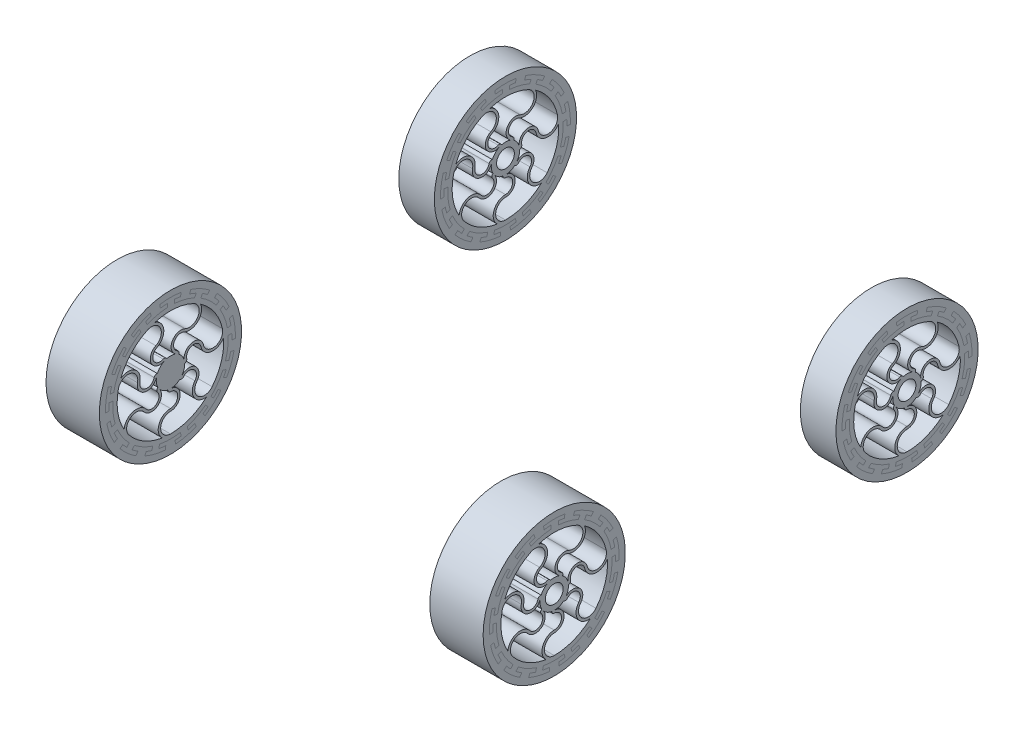
SolidWorks part; units mm, degrees
material "TPU"
ref_plane "Front Plane" through (0, 0, 0) normal (0, 0, 1) x (1, 0, 0)
ref_plane "Top Plane" through (0, 0, 0) normal (0, 1, 0) x (1, 0, 0)
ref_plane "Right Plane" through (0, 0, 0) normal (1, 0, 0) x (0, 0, -1)
ref_plane "Plane1" through (65.3625, 0, 0) normal (1, 0, 0) x (0, 0, -1)
sketch "Sketch1" plane through (65.3625, 0, 0) normal (1, 0, 0) x (0, 0, -1)
  circle A0 centre (0, 0) radius 25.4 construction
  circle A1 centre (0, 0) radius 3.175
  circle A2 centre (0, 0) radius 5.08
  circle A3 centre (0, 0) radius 20.6375
  circle A4 centre (0, 0) radius 19.05
  dimension "D1" = 50.8
  dimension "D2" = 1.5875
  dimension "D3" = 4.7625
  dimension "D4" = 6.35
  dimension "D5" = 10.16
extrude "Boss-Extrude1" add sketch "Sketch1" along normal blind 12.7 contours A3 A4 | A2 A1 region at (65.3625, 0, 4.9363) region at (65.3625, 0, 20.0538)
sketch "Sketch2" plane through (65.3625, 0, 0) normal (1, 0, 0) x (0, 0, -1)
  circle A0 centre (0, 0) radius 5.08
  circle A1 centre (0, 0) radius 19.05
  arc A2 (0, -12.065) -> (0, -5.08) centre (0, -8.5725) ccw
  arc A3 (0, -12.065) -> (0, -19.05) centre (0, -15.5575) ccw
  arc A6 (0, -11.176) -> (-2.919, -18.825) centre (0, -15.5575) ccw
  arc A7 (0, -11.176) -> (0, -5.969) centre (0, -8.5725) ccw
  arc A8 (0, -5.969) -> (-0.8856, -5.0022) centre (0, -5.08) cw
  circle A9 centre (0, 0) radius 19.05 construction
  dimension "D1" = 10.16
  dimension "D3" = 0.889
  dimension "D4" = 0
extrude "Boss-Extrude2" add sketch "Sketch2" along normal up to surface (12.7 mm away) contours A8 A7 A6 A1 A3 A2 A0 region at (65.3625, -11.5929, 0.5056) up to face at (78.0625, 0, -3.175)
pattern_circular "CirPattern1" count 7 over 360 about axis through (78.0625, 0, 0) along (1, 0, 0) of "Boss-Extrude2"
sketch "Sketch3" plane through (65.3625, 0, 0) normal (1, 0, 0) x (0, 0, -1)
  line L2 (-3.81, 22.873) -> (-3.6013, 21.6202)
  line L4 (-1.0968, 21.8907) -> (-1.0968, 20.6083)
  line L6 (3.81, 22.873) -> (3.6013, 21.6202)
  line L7 (1.4432, 21.8706) -> (1.4432, 20.587)
  circle A0 centre (0, 0) radius 20.6375 construction
  circle A1 centre (0, 0) radius 20.6375
  arc A2 (-3.81, 22.873) -> (3.81, 22.873) centre (0, 0) cw
  arc A3 (-3.6013, 21.6202) -> (-1.0968, 21.8907) centre (0, 0) cw
  arc A4 (1.4432, 21.8706) -> (3.6013, 21.6202) centre (0, 0) cw
  point P16 (0, 0)
  point P17 (-3.5825, 23.762)
  dimension "D5" = 2.5401
  dimension "D1" = 2.54
  dimension "D2" = 1.27
  dimension "D3" = 7.62
  dimension "D4" = 2.286
extrude "Boss-Extrude3" add sketch "Sketch3" along a picked direction on the side of the normal blind 12.7 contours A1 L7 L6 A2 L2 A3 L4 region at (65.3625, 22.1515, -0.0444)
pattern_circular "CirPattern2" count 13 over 360 about axis through (78.0625, 0, 0) along (1, 0, 0) of "Boss-Extrude3"
sketch "Sketch5" plane through (65.3625, 0, 0) normal (1, 0, 0) x (0, 0, -1)
  line L36 (-1.0968, 21.8907) -> (-1.0968, 20.6083)
  line L37 (-1.0968, 21.8907) -> (-1.0968, 20.6083)
  line L38 (-3.81, 22.873) -> (-3.6013, 21.6202)
  line L39 (-3.81, 22.873) -> (-3.6013, 21.6202)
  line L40 (3.6013, 21.6202) -> (3.81, 22.873)
  line L41 (3.6013, 21.6202) -> (3.81, 22.873)
  line L42 (1.4432, 20.587) -> (1.4432, 21.8706)
  line L43 (1.4432, 20.587) -> (1.4432, 21.8706)
  line L44 (15.3372, -15.6581) -> (14.4868, -14.6982)
  line L45 (15.3372, -15.6581) -> (14.4868, -14.6982)
  line L46 (18.0194, -14.5942) -> (17.0325, -13.7949)
  line L47 (18.0194, -14.5942) -> (17.0325, -13.7949)
  line L48 (11.6412, -18.5711) -> (12.3158, -19.6472)
  line L49 (11.6412, -18.5711) -> (12.3158, -19.6472)
  line L50 (12.5714, -16.3666) -> (13.4226, -17.3274)
  line L51 (12.5714, -16.3666) -> (13.4226, -17.3274)
  line L52 (6.3037, -20.9921) -> (5.9968, -19.747)
  line L53 (6.3037, -20.9921) -> (5.9968, -19.747)
  line L54 (9.1731, -21.2965) -> (8.6707, -20.1301)
  line L55 (9.1731, -21.2965) -> (8.6707, -20.1301)
  line L56 (1.6774, -21.8538) -> (1.7746, -23.1201)
  line L57 (1.6774, -21.8538) -> (1.7746, -23.1201)
  line L58 (3.5255, -20.3341) -> (3.8327, -21.5804)
  line L59 (3.5255, -20.3341) -> (3.8327, -21.5804)
  line L60 (-4.1738, -21.517) -> (-3.867, -20.272)
  line L61 (-4.1738, -21.517) -> (-3.867, -20.272)
  line L62 (-1.7746, -23.1201) -> (-1.6774, -21.8538)
  line L63 (-1.7746, -23.1201) -> (-1.6774, -21.8538)
  line L64 (-8.6707, -20.1301) -> (-9.1731, -21.2965)
  line L65 (-8.6707, -20.1301) -> (-9.1731, -21.2965)
  line L66 (-6.328, -19.6434) -> (-6.6352, -20.8897)
  line L67 (-6.328, -19.6434) -> (-6.6352, -20.8897)
  line L68 (-13.6952, -17.1127) -> (-12.8449, -16.1529)
  line L69 (-13.6952, -17.1127) -> (-12.8449, -16.1529)
  line L70 (-12.3158, -19.6472) -> (-11.6412, -18.5711)
  line L71 (-12.3158, -19.6472) -> (-11.6412, -18.5711)
  line L108 (-17.0325, -13.7949) -> (-18.0194, -14.5942)
  line L109 (-17.0325, -13.7949) -> (-18.0194, -14.5942)
  line L110 (-14.7319, -14.4526) -> (-15.5831, -15.4133)
  line L111 (-14.7319, -14.4526) -> (-15.5831, -15.4133)
  line L112 (-20.0792, -8.7881) -> (-18.8802, -8.3333)
  line L113 (-20.0792, -8.7881) -> (-18.8802, -8.3333)
  line L114 (-20.0356, -11.6733) -> (-18.9382, -11.0339)
  line L115 (-20.0356, -11.6733) -> (-18.9382, -11.0339)
  line L116 (-21.4923, -4.2993) -> (-22.7376, -4.5485)
  line L117 (-21.4923, -4.2993) -> (-22.7376, -4.5485)
  line L118 (-19.7609, -5.9508) -> (-20.9611, -6.406)
  line L119 (-19.7609, -5.9508) -> (-20.9611, -6.406)
  line L120 (-21.8633, 1.5498) -> (-20.5903, 1.3953)
  line L121 (-21.8633, 1.5498) -> (-20.5903, 1.3953)
  line L122 (-23.1655, -1.0252) -> (-21.8967, -0.969)
  line L123 (-23.1655, -1.0252) -> (-21.8967, -0.969)
  line L124 (-21.0285, 6.1811) -> (-22.247, 6.5393)
  line L125 (-21.0285, 6.1811) -> (-22.247, 6.5393)
  line L126 (-20.2629, 3.9142) -> (-21.5371, 4.0689)
  line L127 (-20.2629, 3.9142) -> (-21.5371, 4.0689)
  line L128 (-18.6387, 11.5327) -> (-17.5834, 10.8042)
  line L129 (-18.6387, 11.5327) -> (-17.5834, 10.8042)
  line L130 (-20.9884, 9.8578) -> (-19.8389, 9.3179)
  line L131 (-20.9884, 9.8578) -> (-19.8389, 9.3179)
  line L132 (-15.7473, 15.2455) -> (-16.6598, 16.1289)
  line L133 (-15.7473, 15.2455) -> (-16.6598, 16.1289)
  line L134 (-16.1229, 12.8825) -> (-17.1793, 13.6116)
  line L135 (-16.1229, 12.8825) -> (-17.1793, 13.6116)
  line L136 (-11.1443, 18.8735) -> (-10.5483, 17.7381)
  line L137 (-11.1443, 18.8735) -> (-10.5483, 17.7381)
  line L138 (-14.0032, 18.4824) -> (-13.2362, 17.4701)
  line L139 (-14.0032, 18.4824) -> (-13.2362, 17.4701)
  line L140 (-6.8586, 20.8174) -> (-7.256, 22.0236)
  line L141 (-6.8586, 20.8174) -> (-7.256, 22.0236)
  line L142 (-8.2894, 18.8995) -> (-8.8859, 20.0361)
  line L143 (-8.2894, 18.8995) -> (-8.8859, 20.0361)
  line L160 (9.2019, 19.8929) -> (8.606, 18.7575)
  line L161 (9.2019, 19.8929) -> (8.606, 18.7575)
  line L162 (7.256, 22.0236) -> (6.8586, 20.8174)
  line L163 (7.256, 22.0236) -> (6.8586, 20.8174)
  line L164 (13.2362, 17.4701) -> (14.0032, 18.4824)
  line L165 (13.2362, 17.4701) -> (14.0032, 18.4824)
  line L166 (10.8451, 17.5582) -> (11.4416, 18.6947)
  line L167 (10.8451, 17.5582) -> (11.4416, 18.6947)
  line L168 (17.3926, 13.338) -> (16.3373, 12.6095)
  line L169 (17.3926, 13.338) -> (16.3373, 12.6095)
  line L170 (16.6598, 16.1289) -> (15.7473, 15.2455)
  line L171 (16.6598, 16.1289) -> (15.7473, 15.2455)
  line L172 (19.8389, 9.3179) -> (20.9884, 9.8578)
  line L173 (19.8389, 9.3179) -> (20.9884, 9.8578)
  line L174 (17.7626, 10.507) -> (18.8189, 11.2362)
  line L175 (17.7626, 10.507) -> (18.8189, 11.2362)
  line L176 (21.5989, 3.7274) -> (20.3259, 3.5729)
  line L177 (21.5989, 3.7274) -> (20.3259, 3.5729)
  line L178 (22.247, 6.5393) -> (21.0285, 6.1811)
  line L179 (22.247, 6.5393) -> (21.0285, 6.1811)
  line L180 (21.8967, -0.969) -> (23.1655, -1.0252)
  line L181 (21.8967, -0.969) -> (23.1655, -1.0252)
  line L182 (20.6108, 1.0488) -> (21.8851, 1.2035)
  line L183 (20.6108, 1.0488) -> (21.8851, 1.2035)
  line L184 (20.8571, -6.737) -> (19.6581, -6.2823)
  line L185 (20.8571, -6.737) -> (19.6581, -6.2823)
  line L186 (22.7376, -4.5485) -> (21.4923, -4.2993)
  line L187 (22.7376, -4.5485) -> (21.4923, -4.2993)
  line L188 (18.9382, -11.0339) -> (20.0356, -11.6733)
  line L189 (18.9382, -11.0339) -> (20.0356, -11.6733)
  line L190 (18.7374, -8.6497) -> (19.9376, -9.1048)
  line L191 (18.7374, -8.6497) -> (19.9376, -9.1048)
  circle A0 centre (0, 0) radius 25.4
  arc A37 (-1.0968, 20.6083) -> (-8.2894, 18.8995) centre (0, 0) ccw
  arc A38 (-1.0968, 21.8907) -> (-3.6013, 21.6202) centre (0, 0) ccw
  arc A39 (-1.0968, 21.8907) -> (-3.6013, 21.6202) centre (0, 0) ccw
  arc A40 (3.81, 22.873) -> (-3.81, 22.873) centre (0, 0) ccw
  arc A41 (3.81, 22.873) -> (-3.81, 22.873) centre (0, 0) ccw
  arc A42 (3.6013, 21.6202) -> (1.4432, 21.8706) centre (0, 0) ccw
  arc A43 (3.6013, 21.6202) -> (1.4432, 21.8706) centre (0, 0) ccw
  arc A44 (8.606, 18.7575) -> (1.4432, 20.587) centre (0, 0) ccw
  arc A45 (8.606, 18.7575) -> (1.4432, 20.587) centre (0, 0) ccw
  arc A46 (15.3372, -15.6581) -> (17.0325, -13.7949) centre (0, 0) ccw
  arc A47 (15.3372, -15.6581) -> (17.0325, -13.7949) centre (0, 0) ccw
  arc A48 (12.3158, -19.6472) -> (18.0194, -14.5942) centre (0, 0) ccw
  arc A49 (12.3158, -19.6472) -> (18.0194, -14.5942) centre (0, 0) ccw
  arc A50 (11.6412, -18.5711) -> (13.4226, -17.3274) centre (0, 0) ccw
  arc A51 (11.6412, -18.5711) -> (13.4226, -17.3274) centre (0, 0) ccw
  arc A52 (5.9968, -19.747) -> (12.5714, -16.3666) centre (0, 0) ccw
  arc A53 (5.9968, -19.747) -> (12.5714, -16.3666) centre (0, 0) ccw
  arc A54 (6.3037, -20.9921) -> (8.6707, -20.1301) centre (0, 0) ccw
  arc A55 (6.3037, -20.9921) -> (8.6707, -20.1301) centre (0, 0) ccw
  arc A56 (1.7746, -23.1201) -> (9.1731, -21.2965) centre (0, 0) ccw
  arc A57 (1.7746, -23.1201) -> (9.1731, -21.2965) centre (0, 0) ccw
  arc A58 (1.6774, -21.8538) -> (3.8327, -21.5804) centre (0, 0) ccw
  arc A59 (1.6774, -21.8538) -> (3.8327, -21.5804) centre (0, 0) ccw
  arc A60 (-3.867, -20.272) -> (3.5255, -20.3341) centre (0, 0) ccw
  arc A61 (-3.867, -20.272) -> (3.5255, -20.3341) centre (0, 0) ccw
  arc A62 (-4.1738, -21.517) -> (-1.6774, -21.8538) centre (0, 0) ccw
  arc A63 (-4.1738, -21.517) -> (-1.6774, -21.8538) centre (0, 0) ccw
  arc A64 (-9.1731, -21.2965) -> (-1.7746, -23.1201) centre (0, 0) ccw
  arc A65 (-9.1731, -21.2965) -> (-1.7746, -23.1201) centre (0, 0) ccw
  arc A66 (-8.6707, -20.1301) -> (-6.6352, -20.8897) centre (0, 0) ccw
  arc A67 (-8.6707, -20.1301) -> (-6.6352, -20.8897) centre (0, 0) ccw
  arc A68 (-12.8449, -16.1529) -> (-6.328, -19.6434) centre (0, 0) ccw
  arc A69 (-12.8449, -16.1529) -> (-6.328, -19.6434) centre (0, 0) ccw
  arc A70 (-13.6952, -17.1127) -> (-11.6412, -18.5711) centre (0, 0) ccw
  arc A71 (-13.6952, -17.1127) -> (-11.6412, -18.5711) centre (0, 0) ccw
  arc A72 (-18.0194, -14.5942) -> (-12.3158, -19.6472) centre (0, 0) ccw
  arc A73 (-1.0968, 20.6083) -> (-8.2894, 18.8995) centre (0, 0) ccw
  arc A109 (-18.0194, -14.5942) -> (-12.3158, -19.6472) centre (0, 0) ccw
  arc A110 (-17.0325, -13.7949) -> (-15.5831, -15.4133) centre (0, 0) ccw
  arc A111 (-17.0325, -13.7949) -> (-15.5831, -15.4133) centre (0, 0) ccw
  arc A112 (-18.8802, -8.3333) -> (-14.7319, -14.4526) centre (0, 0) ccw
  arc A113 (-18.8802, -8.3333) -> (-14.7319, -14.4526) centre (0, 0) ccw
  arc A114 (-20.0792, -8.7881) -> (-18.9382, -11.0339) centre (0, 0) ccw
  arc A115 (-20.0792, -8.7881) -> (-18.9382, -11.0339) centre (0, 0) ccw
  arc A116 (-22.7376, -4.5485) -> (-20.0356, -11.6733) centre (0, 0) ccw
  arc A117 (-22.7376, -4.5485) -> (-20.0356, -11.6733) centre (0, 0) ccw
  arc A118 (-21.4923, -4.2993) -> (-20.9611, -6.406) centre (0, 0) ccw
  arc A119 (-21.4923, -4.2993) -> (-20.9611, -6.406) centre (0, 0) ccw
  arc A120 (-20.5903, 1.3953) -> (-19.7609, -5.9508) centre (0, 0) ccw
  arc A121 (-20.5903, 1.3953) -> (-19.7609, -5.9508) centre (0, 0) ccw
  arc A122 (-21.8633, 1.5498) -> (-21.8967, -0.969) centre (0, 0) ccw
  arc A123 (-21.8633, 1.5498) -> (-21.8967, -0.969) centre (0, 0) ccw
  arc A124 (-22.247, 6.5393) -> (-23.1655, -1.0252) centre (0, 0) ccw
  arc A125 (-22.247, 6.5393) -> (-23.1655, -1.0252) centre (0, 0) ccw
  arc A126 (-21.0285, 6.1811) -> (-21.5371, 4.0689) centre (0, 0) ccw
  arc A127 (-21.0285, 6.1811) -> (-21.5371, 4.0689) centre (0, 0) ccw
  arc A128 (-17.5834, 10.8042) -> (-20.2629, 3.9142) centre (0, 0) ccw
  arc A129 (-17.5834, 10.8042) -> (-20.2629, 3.9142) centre (0, 0) ccw
  arc A130 (-18.6387, 11.5327) -> (-19.8389, 9.3179) centre (0, 0) ccw
  arc A131 (-18.6387, 11.5327) -> (-19.8389, 9.3179) centre (0, 0) ccw
  arc A132 (-16.6598, 16.1289) -> (-20.9884, 9.8578) centre (0, 0) ccw
  arc A133 (-16.6598, 16.1289) -> (-20.9884, 9.8578) centre (0, 0) ccw
  arc A134 (-15.7473, 15.2455) -> (-17.1793, 13.6116) centre (0, 0) ccw
  arc A135 (-15.7473, 15.2455) -> (-17.1793, 13.6116) centre (0, 0) ccw
  arc A136 (-10.5483, 17.7381) -> (-16.1229, 12.8825) centre (0, 0) ccw
  arc A137 (-10.5483, 17.7381) -> (-16.1229, 12.8825) centre (0, 0) ccw
  arc A138 (-11.1443, 18.8735) -> (-13.2362, 17.4701) centre (0, 0) ccw
  arc A139 (-11.1443, 18.8735) -> (-13.2362, 17.4701) centre (0, 0) ccw
  arc A140 (-7.256, 22.0236) -> (-14.0032, 18.4824) centre (0, 0) ccw
  arc A141 (-7.256, 22.0236) -> (-14.0032, 18.4824) centre (0, 0) ccw
  arc A142 (-6.8586, 20.8174) -> (-8.8859, 20.0361) centre (0, 0) ccw
  arc A143 (-6.8586, 20.8174) -> (-8.8859, 20.0361) centre (0, 0) ccw
  arc A160 (9.2019, 19.8929) -> (6.8586, 20.8174) centre (0, 0) ccw
  arc A161 (9.2019, 19.8929) -> (6.8586, 20.8174) centre (0, 0) ccw
  arc A162 (14.0032, 18.4824) -> (7.256, 22.0236) centre (0, 0) ccw
  arc A163 (14.0032, 18.4824) -> (7.256, 22.0236) centre (0, 0) ccw
  arc A164 (13.2362, 17.4701) -> (11.4416, 18.6947) centre (0, 0) ccw
  arc A165 (13.2362, 17.4701) -> (11.4416, 18.6947) centre (0, 0) ccw
  arc A166 (16.3373, 12.6095) -> (10.8451, 17.5582) centre (0, 0) ccw
  arc A167 (16.3373, 12.6095) -> (10.8451, 17.5582) centre (0, 0) ccw
  arc A168 (17.3926, 13.338) -> (15.7473, 15.2455) centre (0, 0) ccw
  arc A169 (17.3926, 13.338) -> (15.7473, 15.2455) centre (0, 0) ccw
  arc A170 (20.9884, 9.8578) -> (16.6598, 16.1289) centre (0, 0) ccw
  arc A171 (20.9884, 9.8578) -> (16.6598, 16.1289) centre (0, 0) ccw
  arc A172 (19.8389, 9.3179) -> (18.8189, 11.2362) centre (0, 0) ccw
  arc A173 (19.8389, 9.3179) -> (18.8189, 11.2362) centre (0, 0) ccw
  arc A174 (20.3259, 3.5729) -> (17.7626, 10.507) centre (0, 0) ccw
  arc A175 (20.3259, 3.5729) -> (17.7626, 10.507) centre (0, 0) ccw
  arc A176 (21.5989, 3.7274) -> (21.0285, 6.1811) centre (0, 0) ccw
  arc A177 (21.5989, 3.7274) -> (21.0285, 6.1811) centre (0, 0) ccw
  arc A178 (23.1655, -1.0252) -> (22.247, 6.5393) centre (0, 0) ccw
  arc A179 (23.1655, -1.0252) -> (22.247, 6.5393) centre (0, 0) ccw
  arc A180 (21.8967, -0.969) -> (21.8851, 1.2035) centre (0, 0) ccw
  arc A181 (21.8967, -0.969) -> (21.8851, 1.2035) centre (0, 0) ccw
  arc A182 (19.6581, -6.2823) -> (20.6108, 1.0488) centre (0, 0) ccw
  arc A183 (19.6581, -6.2823) -> (20.6108, 1.0488) centre (0, 0) ccw
  arc A184 (20.8571, -6.737) -> (21.4923, -4.2993) centre (0, 0) ccw
  arc A185 (20.8571, -6.737) -> (21.4923, -4.2993) centre (0, 0) ccw
  arc A186 (20.0356, -11.6733) -> (22.7376, -4.5485) centre (0, 0) ccw
  arc A187 (20.0356, -11.6733) -> (22.7376, -4.5485) centre (0, 0) ccw
  arc A188 (18.9382, -11.0339) -> (19.9376, -9.1048) centre (0, 0) ccw
  arc A189 (18.9382, -11.0339) -> (19.9376, -9.1048) centre (0, 0) ccw
  arc A190 (14.4868, -14.6982) -> (18.7374, -8.6497) centre (0, 0) ccw
  arc A191 (14.4868, -14.6982) -> (18.7374, -8.6497) centre (0, 0) ccw
  dimension "D1" = 50.8
  dimension "D2" = 0
extrude "Boss-Extrude4" add sketch "Sketch5" along normal up to surface (12.7 mm away) separate body up to face at (78.0625, -9.1625, 4.7382)
sketch "Sketch4" plane through (0, 0, 0) normal (1, 0, 0) x (0, 0, -1)
  line L0 (0, 0) -> (-126, 0) construction
pattern_linear "LPattern1" count 2 spacing 126 along (0, 0, 1) of bodies 111 107
sketch "Sketch6" plane through (65.3625, 0, 0) normal (-1, 0, 0) x (0, 0, 1)
  line L36 (127.0968, 20.6083) -> (127.0968, 21.8907)
  line L37 (129.6013, 21.6202) -> (129.81, 22.873)
  line L38 (122.19, 22.873) -> (122.3987, 21.6202)
  line L39 (124.5568, 21.8706) -> (124.5568, 20.587)
  line L40 (111.5132, -14.6982) -> (110.6628, -15.6581)
  line L41 (108.9675, -13.7949) -> (107.9806, -14.5942)
  line L42 (113.6842, -19.6472) -> (114.3588, -18.5711)
  line L43 (112.5774, -17.3274) -> (113.4286, -16.3666)
  line L44 (120.0032, -19.747) -> (119.6963, -20.9921)
  line L45 (117.3293, -20.1301) -> (116.8268, -21.2965)
  line L46 (124.2254, -23.1201) -> (124.3226, -21.8538)
  line L47 (122.1673, -21.5804) -> (122.4745, -20.3341)
  line L48 (129.867, -20.272) -> (130.1738, -21.517)
  line L49 (127.6774, -21.8538) -> (127.7746, -23.1201)
  line L50 (135.1731, -21.2965) -> (134.6707, -20.1301)
  line L51 (132.6352, -20.8897) -> (132.328, -19.6434)
  line L52 (138.8449, -16.1529) -> (139.6952, -17.1127)
  line L53 (137.6412, -18.5711) -> (138.3158, -19.6472)
  line L54 (144.0194, -14.5942) -> (143.0325, -13.7949)
  line L55 (141.5831, -15.4133) -> (140.7319, -14.4526)
  line L56 (144.8802, -8.3333) -> (146.0792, -8.7881)
  line L57 (144.9382, -11.0339) -> (146.0356, -11.6733)
  line L58 (148.7376, -4.5485) -> (147.4923, -4.2993)
  line L59 (146.9611, -6.406) -> (145.7609, -5.9508)
  line L60 (146.5903, 1.3953) -> (147.8633, 1.5498)
  line L61 (147.8967, -0.969) -> (149.1654, -1.0252)
  line L62 (148.247, 6.5393) -> (147.0285, 6.1811)
  line L63 (147.5371, 4.0689) -> (146.2629, 3.9142)
  line L64 (143.5834, 10.8042) -> (144.6387, 11.5327)
  line L65 (145.8389, 9.3179) -> (146.9884, 9.8578)
  line L66 (142.6598, 16.1289) -> (141.7473, 15.2455)
  line L67 (143.1793, 13.6116) -> (142.1229, 12.8825)
  line L68 (136.5483, 17.7381) -> (137.1443, 18.8735)
  line L69 (139.2362, 17.4701) -> (140.0032, 18.4824)
  line L70 (133.256, 22.0236) -> (132.8586, 20.8174)
  line L71 (134.8859, 20.0361) -> (134.2894, 18.8995)
  line L72 (127.0968, 20.6083) -> (127.0968, 21.8907)
  line L73 (129.6013, 21.6202) -> (129.81, 22.873)
  line L74 (122.19, 22.873) -> (122.3987, 21.6202)
  line L75 (124.5568, 21.8706) -> (124.5568, 20.587)
  line L76 (111.5132, -14.6982) -> (110.6628, -15.6581)
  line L77 (108.9675, -13.7949) -> (107.9806, -14.5942)
  line L78 (113.6842, -19.6472) -> (114.3588, -18.5711)
  line L79 (112.5774, -17.3274) -> (113.4286, -16.3666)
  line L80 (120.0032, -19.747) -> (119.6963, -20.9921)
  line L81 (117.3293, -20.1301) -> (116.8268, -21.2965)
  line L82 (124.2254, -23.1201) -> (124.3226, -21.8538)
  line L83 (122.1673, -21.5804) -> (122.4745, -20.3341)
  line L84 (129.867, -20.272) -> (130.1738, -21.517)
  line L85 (127.6774, -21.8538) -> (127.7746, -23.1201)
  line L86 (135.1731, -21.2965) -> (134.6707, -20.1301)
  line L87 (132.6352, -20.8897) -> (132.328, -19.6434)
  line L88 (138.8449, -16.1529) -> (139.6952, -17.1127)
  line L89 (137.6412, -18.5711) -> (138.3158, -19.6472)
  line L90 (144.0194, -14.5942) -> (143.0325, -13.7949)
  line L91 (141.5831, -15.4133) -> (140.7319, -14.4526)
  line L92 (144.8802, -8.3333) -> (146.0792, -8.7881)
  line L93 (144.9382, -11.0339) -> (146.0356, -11.6733)
  line L94 (148.7376, -4.5485) -> (147.4923, -4.2993)
  line L95 (146.9611, -6.406) -> (145.7609, -5.9508)
  line L96 (146.5903, 1.3953) -> (147.8633, 1.5498)
  line L97 (147.8967, -0.969) -> (149.1654, -1.0252)
  line L98 (148.247, 6.5393) -> (147.0285, 6.1811)
  line L99 (147.5371, 4.0689) -> (146.2629, 3.9142)
  line L100 (143.5834, 10.8042) -> (144.6387, 11.5327)
  line L101 (145.8389, 9.3179) -> (146.9884, 9.8578)
  line L102 (142.6598, 16.1289) -> (141.7473, 15.2455)
  line L103 (143.1793, 13.6116) -> (142.1229, 12.8825)
  line L104 (136.5483, 17.7381) -> (137.1443, 18.8735)
  line L105 (139.2362, 17.4701) -> (140.0032, 18.4824)
  line L106 (133.256, 22.0236) -> (132.8586, 20.8174)
  line L107 (134.8859, 20.0361) -> (134.2894, 18.8995)
  line L124 (117.394, 18.7575) -> (116.7981, 19.8929)
  line L125 (117.394, 18.7575) -> (116.7981, 19.8929)
  line L126 (119.1414, 20.8174) -> (118.744, 22.0236)
  line L127 (119.1414, 20.8174) -> (118.744, 22.0236)
  line L128 (111.9968, 18.4824) -> (112.7638, 17.4701)
  line L129 (111.9968, 18.4824) -> (112.7638, 17.4701)
  line L130 (114.5584, 18.6947) -> (115.1549, 17.5582)
  line L131 (114.5584, 18.6947) -> (115.1549, 17.5582)
  line L132 (109.6627, 12.6095) -> (108.6074, 13.338)
  line L133 (109.6627, 12.6095) -> (108.6074, 13.338)
  line L134 (110.2527, 15.2455) -> (109.3402, 16.1289)
  line L135 (110.2527, 15.2455) -> (109.3402, 16.1289)
  line L136 (105.0116, 9.8578) -> (106.1611, 9.3179)
  line L137 (105.0116, 9.8578) -> (106.1611, 9.3179)
  line L138 (107.1811, 11.2362) -> (108.2374, 10.507)
  line L139 (107.1811, 11.2362) -> (108.2374, 10.507)
  line L140 (105.6741, 3.5729) -> (104.4011, 3.7274)
  line L141 (105.6741, 3.5729) -> (104.4011, 3.7274)
  line L142 (104.9715, 6.1811) -> (103.753, 6.5393)
  line L143 (104.9715, 6.1811) -> (103.753, 6.5393)
  line L144 (102.8345, -1.0252) -> (104.1033, -0.969)
  line L145 (102.8345, -1.0252) -> (104.1033, -0.969)
  line L146 (104.1149, 1.2035) -> (105.3892, 1.0488)
  line L147 (104.1149, 1.2035) -> (105.3892, 1.0488)
  line L148 (106.3419, -6.2823) -> (105.1429, -6.737)
  line L149 (106.3419, -6.2823) -> (105.1429, -6.737)
  line L150 (104.5077, -4.2993) -> (103.2623, -4.5485)
  line L151 (104.5077, -4.2993) -> (103.2623, -4.5485)
  line L152 (105.9644, -11.6733) -> (107.0618, -11.0339)
  line L153 (105.9644, -11.6733) -> (107.0618, -11.0339)
  line L154 (106.0624, -9.1048) -> (107.2626, -8.6497)
  line L155 (106.0624, -9.1048) -> (107.2626, -8.6497)
  arc A36 (134.2894, 18.8995) -> (127.0968, 20.6083) centre (126, 0) ccw
  arc A37 (129.6013, 21.6202) -> (127.0968, 21.8907) centre (126, 0) ccw
  arc A38 (129.81, 22.873) -> (122.19, 22.873) centre (126, 0) ccw
  arc A39 (124.5568, 21.8706) -> (122.3987, 21.6202) centre (126, 0) ccw
  arc A40 (124.5568, 20.587) -> (117.394, 18.7575) centre (126, 0) ccw
  arc A41 (108.9675, -13.7949) -> (110.6628, -15.6581) centre (126, 0) ccw
  arc A42 (107.9806, -14.5942) -> (113.6842, -19.6472) centre (126, 0) ccw
  arc A43 (112.5774, -17.3274) -> (114.3588, -18.5711) centre (126, 0) ccw
  arc A44 (113.4286, -16.3666) -> (120.0032, -19.747) centre (126, 0) ccw
  arc A45 (117.3293, -20.1301) -> (119.6963, -20.9921) centre (126, 0) ccw
  arc A46 (116.8268, -21.2965) -> (124.2254, -23.1201) centre (126, 0) ccw
  arc A47 (122.1673, -21.5804) -> (124.3226, -21.8538) centre (126, 0) ccw
  arc A48 (122.4745, -20.3341) -> (129.867, -20.272) centre (126, 0) ccw
  arc A49 (127.6774, -21.8538) -> (130.1738, -21.517) centre (126, 0) ccw
  arc A50 (127.7746, -23.1201) -> (135.1731, -21.2965) centre (126, 0) ccw
  arc A51 (132.6352, -20.8897) -> (134.6707, -20.1301) centre (126, 0) ccw
  arc A52 (132.328, -19.6434) -> (138.8449, -16.1529) centre (126, 0) ccw
  arc A53 (137.6412, -18.5711) -> (139.6952, -17.1127) centre (126, 0) ccw
  arc A54 (138.3158, -19.6472) -> (144.0194, -14.5942) centre (126, 0) ccw
  arc A55 (141.5831, -15.4133) -> (143.0325, -13.7949) centre (126, 0) ccw
  arc A56 (140.7319, -14.4526) -> (144.8802, -8.3333) centre (126, 0) ccw
  arc A57 (144.9382, -11.0339) -> (146.0792, -8.7881) centre (126, 0) ccw
  arc A58 (146.0356, -11.6733) -> (148.7376, -4.5485) centre (126, 0) ccw
  arc A59 (146.9611, -6.406) -> (147.4923, -4.2993) centre (126, 0) ccw
  arc A60 (145.7609, -5.9508) -> (146.5903, 1.3953) centre (126, 0) ccw
  arc A61 (147.8967, -0.969) -> (147.8633, 1.5498) centre (126, 0) ccw
  arc A62 (149.1654, -1.0252) -> (148.247, 6.5393) centre (126, 0) ccw
  arc A63 (147.5371, 4.0689) -> (147.0285, 6.1811) centre (126, 0) ccw
  arc A64 (146.2629, 3.9142) -> (143.5834, 10.8042) centre (126, 0) ccw
  arc A65 (145.8389, 9.3179) -> (144.6387, 11.5327) centre (126, 0) ccw
  arc A66 (146.9884, 9.8578) -> (142.6598, 16.1289) centre (126, 0) ccw
  arc A67 (143.1793, 13.6116) -> (141.7473, 15.2455) centre (126, 0) ccw
  arc A68 (142.1229, 12.8825) -> (136.5483, 17.7381) centre (126, 0) ccw
  arc A69 (139.2362, 17.4701) -> (137.1443, 18.8735) centre (126, 0) ccw
  arc A70 (140.0032, 18.4824) -> (133.256, 22.0236) centre (126, 0) ccw
  arc A71 (134.8859, 20.0361) -> (132.8586, 20.8174) centre (126, 0) ccw
  arc A72 (134.2894, 18.8995) -> (127.0968, 20.6083) centre (126, 0) ccw
  arc A73 (129.6013, 21.6202) -> (127.0968, 21.8907) centre (126, 0) ccw
  arc A74 (129.81, 22.873) -> (122.19, 22.873) centre (126, 0) ccw
  arc A75 (124.5568, 21.8706) -> (122.3987, 21.6202) centre (126, 0) ccw
  arc A76 (124.5568, 20.587) -> (117.394, 18.7575) centre (126, 0) ccw
  arc A77 (108.9675, -13.7949) -> (110.6628, -15.6581) centre (126, 0) ccw
  arc A78 (107.9806, -14.5942) -> (113.6842, -19.6472) centre (126, 0) ccw
  arc A79 (112.5774, -17.3274) -> (114.3588, -18.5711) centre (126, 0) ccw
  arc A80 (113.4286, -16.3666) -> (120.0032, -19.747) centre (126, 0) ccw
  arc A81 (117.3293, -20.1301) -> (119.6963, -20.9921) centre (126, 0) ccw
  arc A82 (116.8268, -21.2965) -> (124.2254, -23.1201) centre (126, 0) ccw
  arc A83 (122.1673, -21.5804) -> (124.3226, -21.8538) centre (126, 0) ccw
  arc A84 (122.4745, -20.3341) -> (129.867, -20.272) centre (126, 0) ccw
  arc A85 (127.6774, -21.8538) -> (130.1738, -21.517) centre (126, 0) ccw
  arc A86 (127.7746, -23.1201) -> (135.1731, -21.2965) centre (126, 0) ccw
  arc A87 (132.6352, -20.8897) -> (134.6707, -20.1301) centre (126, 0) ccw
  arc A88 (132.328, -19.6434) -> (138.8449, -16.1529) centre (126, 0) ccw
  arc A89 (137.6412, -18.5711) -> (139.6952, -17.1127) centre (126, 0) ccw
  arc A90 (138.3158, -19.6472) -> (144.0194, -14.5942) centre (126, 0) ccw
  arc A91 (141.5831, -15.4133) -> (143.0325, -13.7949) centre (126, 0) ccw
  arc A92 (140.7319, -14.4526) -> (144.8802, -8.3333) centre (126, 0) ccw
  arc A93 (144.9382, -11.0339) -> (146.0792, -8.7881) centre (126, 0) ccw
  arc A94 (146.0356, -11.6733) -> (148.7376, -4.5485) centre (126, 0) ccw
  arc A95 (146.9611, -6.406) -> (147.4923, -4.2993) centre (126, 0) ccw
  arc A96 (145.7609, -5.9508) -> (146.5903, 1.3953) centre (126, 0) ccw
  arc A97 (147.8967, -0.969) -> (147.8633, 1.5498) centre (126, 0) ccw
  arc A98 (149.1654, -1.0252) -> (148.247, 6.5393) centre (126, 0) ccw
  arc A99 (147.5371, 4.0689) -> (147.0285, 6.1811) centre (126, 0) ccw
  arc A100 (146.2629, 3.9142) -> (143.5834, 10.8042) centre (126, 0) ccw
  arc A101 (145.8389, 9.3179) -> (144.6387, 11.5327) centre (126, 0) ccw
  arc A102 (146.9884, 9.8578) -> (142.6598, 16.1289) centre (126, 0) ccw
  arc A103 (143.1793, 13.6116) -> (141.7473, 15.2455) centre (126, 0) ccw
  arc A104 (142.1229, 12.8825) -> (136.5483, 17.7381) centre (126, 0) ccw
  arc A105 (139.2362, 17.4701) -> (137.1443, 18.8735) centre (126, 0) ccw
  arc A106 (140.0032, 18.4824) -> (133.256, 22.0236) centre (126, 0) ccw
  arc A107 (134.8859, 20.0361) -> (132.8586, 20.8174) centre (126, 0) ccw
  arc A124 (119.1414, 20.8174) -> (116.7981, 19.8929) centre (126, 0) ccw
  arc A125 (119.1414, 20.8174) -> (116.7981, 19.8929) centre (126, 0) ccw
  arc A126 (118.744, 22.0236) -> (111.9968, 18.4824) centre (126, 0) ccw
  arc A127 (118.744, 22.0236) -> (111.9968, 18.4824) centre (126, 0) ccw
  arc A128 (114.5584, 18.6947) -> (112.7638, 17.4701) centre (126, 0) ccw
  arc A129 (114.5584, 18.6947) -> (112.7638, 17.4701) centre (126, 0) ccw
  arc A130 (115.1549, 17.5582) -> (109.6627, 12.6095) centre (126, 0) ccw
  arc A131 (115.1549, 17.5582) -> (109.6627, 12.6095) centre (126, 0) ccw
  arc A132 (110.2527, 15.2455) -> (108.6074, 13.338) centre (126, 0) ccw
  arc A133 (110.2527, 15.2455) -> (108.6074, 13.338) centre (126, 0) ccw
  arc A134 (109.3402, 16.1289) -> (105.0116, 9.8578) centre (126, 0) ccw
  arc A135 (109.3402, 16.1289) -> (105.0116, 9.8578) centre (126, 0) ccw
  arc A136 (107.1811, 11.2362) -> (106.1611, 9.3179) centre (126, 0) ccw
  arc A137 (107.1811, 11.2362) -> (106.1611, 9.3179) centre (126, 0) ccw
  arc A138 (108.2374, 10.507) -> (105.6741, 3.5729) centre (126, 0) ccw
  arc A139 (108.2374, 10.507) -> (105.6741, 3.5729) centre (126, 0) ccw
  arc A140 (104.9715, 6.1811) -> (104.4011, 3.7274) centre (126, 0) ccw
  arc A141 (104.9715, 6.1811) -> (104.4011, 3.7274) centre (126, 0) ccw
  arc A142 (103.753, 6.5393) -> (102.8345, -1.0252) centre (126, 0) ccw
  arc A143 (103.753, 6.5393) -> (102.8345, -1.0252) centre (126, 0) ccw
  arc A144 (104.1149, 1.2035) -> (104.1033, -0.969) centre (126, 0) ccw
  arc A145 (104.1149, 1.2035) -> (104.1033, -0.969) centre (126, 0) ccw
  arc A146 (105.3892, 1.0488) -> (106.3419, -6.2823) centre (126, 0) ccw
  arc A147 (105.3892, 1.0488) -> (106.3419, -6.2823) centre (126, 0) ccw
  arc A148 (104.5077, -4.2993) -> (105.1429, -6.737) centre (126, 0) ccw
  arc A149 (104.5077, -4.2993) -> (105.1429, -6.737) centre (126, 0) ccw
  arc A150 (103.2623, -4.5485) -> (105.9644, -11.6733) centre (126, 0) ccw
  arc A151 (103.2623, -4.5485) -> (105.9644, -11.6733) centre (126, 0) ccw
  arc A152 (106.0624, -9.1048) -> (107.0618, -11.0339) centre (126, 0) ccw
  arc A153 (106.0624, -9.1048) -> (107.0618, -11.0339) centre (126, 0) ccw
  arc A154 (107.2626, -8.6497) -> (111.5132, -14.6982) centre (126, 0) ccw
  arc A155 (107.2626, -8.6497) -> (111.5132, -14.6982) centre (126, 0) ccw
  dimension "D1" = 0
extrude "Boss-Extrude6" add sketch "Sketch6" along normal up to surface (6.35 mm away)
sketch "Sketch9" plane through (65.3625, 0, 0) normal (1, 0, 0) x (0, 0, -1)
  arc A0 (-128.2041, 4.5769) -> (-130.6797, 1.9765) centre (-126, 0) ccw construction
  arc A1 (-131.2348, 10.8702) -> (-128.2041, 4.5769) centre (-129.7195, 7.7236) ccw construction
  arc A2 (-131.2348, 10.8702) -> (-134.2655, 17.1635) centre (-132.7501, 14.0168) ccw construction
  arc A3 (-134.2655, 17.1635) -> (-143.7035, 7.0348) centre (-126, 0) ccw construction
  arc A4 (-136.8958, 2.4869) -> (-143.7035, 7.0348) centre (-141.1674, 3.4619) ccw construction
  arc A5 (-136.8958, 2.4869) -> (-131.8193, 1.3282) centre (-134.3576, 1.9076) ccw construction
  arc A6 (-130.6797, 1.9765) -> (-131.8193, 1.3282) centre (-130.9526, 1.1304) ccw construction
  arc A7 (-130.9526, 1.1304) -> (-130.463, -2.4264) centre (-126, 0) ccw construction
  arc A8 (-137.7625, 2.6847) -> (-130.9526, 1.1304) centre (-134.3576, 1.9076) ccw construction
  arc A9 (-137.7625, 2.6847) -> (-144.5724, 4.239) centre (-141.1674, 3.4619) ccw construction
  arc A10 (-144.5724, 4.239) -> (-142.538, -9.455) centre (-126, 0) ccw construction
  arc A11 (-134.7377, -6.9681) -> (-142.538, -9.455) centre (-138.1633, -9.6999) ccw construction
  arc A12 (-134.7377, -6.9681) -> (-130.6668, -3.7216) centre (-132.7022, -5.3449) ccw construction
  arc A13 (-130.463, -2.4264) -> (-130.6668, -3.7216) centre (-129.9717, -3.1673) ccw construction
  arc A14 (-140.8939, -11.8775) -> (-128.919, -18.825) centre (-126, 0) ccw construction
  arc A15 (-126, -11.176) -> (-128.919, -18.825) centre (-126, -15.5575) ccw construction
  arc A16 (-126, -11.176) -> (-126, -5.969) centre (-126, -8.5725) ccw construction
  arc A17 (-126.8856, -5.0022) -> (-126, -5.969) centre (-126, -5.08) ccw construction
  arc A18 (-129.9717, -3.1673) -> (-126.8856, -5.0022) centre (-126, 0) ccw construction
  arc A19 (-135.4328, -7.5224) -> (-129.9717, -3.1673) centre (-132.7022, -5.3449) ccw construction
  arc A20 (-135.4328, -7.5224) -> (-140.8939, -11.8775) centre (-138.1633, -9.6999) ccw construction
  arc A21 (-126, -12.065) -> (-126, -19.05) centre (-126, -15.5575) ccw construction
  arc A22 (-126, -19.05) -> (-113.102, -14.0194) centre (-126, 0) ccw construction
  arc A23 (-117.2623, -6.9681) -> (-113.102, -14.0194) centre (-113.8367, -9.6999) ccw construction
  arc A24 (-117.2623, -6.9681) -> (-121.3332, -3.7216) centre (-119.2977, -5.3449) ccw construction
  arc A25 (-122.6413, -3.8112) -> (-121.3332, -3.7216) centre (-122.0283, -3.1673) ccw construction
  arc A26 (-126, -5.08) -> (-122.6413, -3.8112) centre (-126, 0) ccw construction
  arc A27 (-126, -12.065) -> (-126, -5.08) centre (-126, -8.5725) ccw construction
  arc A28 (-122.0283, -3.1673) -> (-120.9261, 0.2497) centre (-126, 0) ccw construction
  arc A29 (-116.5672, -7.5224) -> (-122.0283, -3.1673) centre (-119.2977, -5.3449) ccw construction
  arc A30 (-116.5672, -7.5224) -> (-111.1061, -11.8775) centre (-113.8367, -9.6999) ccw construction
  arc A31 (-111.1061, -11.8775) -> (-106.9974, 1.3431) centre (-126, 0) ccw construction
  arc A32 (-115.1042, 2.4869) -> (-106.9974, 1.3431) centre (-110.8326, 3.4619) ccw construction
  arc A33 (-115.1042, 2.4869) -> (-120.1807, 1.3282) centre (-117.6424, 1.9076) ccw construction
  arc A34 (-120.9261, 0.2497) -> (-120.1807, 1.3282) centre (-121.0474, 1.1304) ccw construction
  arc A35 (-121.0474, 1.1304) -> (-123.0317, 4.1226) centre (-126, 0) ccw construction
  arc A36 (-114.2375, 2.6847) -> (-121.0474, 1.1304) centre (-117.6424, 1.9076) ccw construction
  arc A37 (-114.2375, 2.6847) -> (-107.4276, 4.239) centre (-110.8326, 3.4619) ccw construction
  arc A38 (-107.4276, 4.239) -> (-115.2022, 15.6942) centre (-126, 0) ccw construction
  arc A39 (-121.1509, 10.0692) -> (-115.2022, 15.6942) centre (-119.2499, 14.0168) ccw construction
  arc A40 (-121.1509, 10.0692) -> (-123.4101, 5.3779) centre (-122.2805, 7.7236) ccw construction
  arc A41 (-123.0317, 4.1226) -> (-123.4101, 5.3779) centre (-123.7959, 4.5769) ccw construction
  arc A42 (-123.7959, 4.5769) -> (-127.3725, 4.8911) centre (-126, 0) ccw construction
  arc A43 (-120.7652, 10.8702) -> (-123.7959, 4.5769) centre (-122.2805, 7.7236) ccw construction
  arc A44 (-120.7652, 10.8702) -> (-117.7345, 17.1635) centre (-119.2499, 14.0168) ccw construction
  arc A45 (-117.7345, 17.1635) -> (-131.5379, 18.2273) centre (-126, 0) ccw construction
  arc A46 (-130.8491, 10.0692) -> (-131.5379, 18.2273) centre (-132.7501, 14.0168) ccw construction
  arc A47 (-130.8491, 10.0692) -> (-128.5899, 5.3779) centre (-129.7195, 7.7236) ccw construction
  arc A48 (-127.3725, 4.8911) -> (-128.5899, 5.3779) centre (-128.2041, 4.5769) ccw construction
  arc A49 (-128.2041, 4.5769) -> (-130.6797, 1.9765) centre (-126, 0) ccw
  arc A50 (-131.2348, 10.8702) -> (-128.2041, 4.5769) centre (-129.7195, 7.7236) ccw
  arc A51 (-131.2348, 10.8702) -> (-134.2655, 17.1635) centre (-132.7501, 14.0168) ccw
  arc A52 (-134.2655, 17.1635) -> (-143.7035, 7.0348) centre (-126, 0) ccw
  arc A53 (-136.8958, 2.4869) -> (-143.7035, 7.0348) centre (-141.1674, 3.4619) ccw
  arc A54 (-136.8958, 2.4869) -> (-131.8193, 1.3282) centre (-134.3576, 1.9076) ccw
  arc A55 (-130.6797, 1.9765) -> (-131.8193, 1.3282) centre (-130.9526, 1.1304) ccw
  arc A56 (-130.9526, 1.1304) -> (-130.463, -2.4264) centre (-126, 0) ccw
  arc A57 (-137.7625, 2.6847) -> (-130.9526, 1.1304) centre (-134.3576, 1.9076) ccw
  arc A58 (-137.7625, 2.6847) -> (-144.5724, 4.239) centre (-141.1674, 3.4619) ccw
  arc A59 (-144.5724, 4.239) -> (-142.538, -9.455) centre (-126, 0) ccw
  arc A60 (-134.7377, -6.9681) -> (-142.538, -9.455) centre (-138.1633, -9.6999) ccw
  arc A61 (-134.7377, -6.9681) -> (-130.6668, -3.7216) centre (-132.7022, -5.3449) ccw
  arc A62 (-130.463, -2.4264) -> (-130.6668, -3.7216) centre (-129.9717, -3.1673) ccw
  arc A63 (-140.8939, -11.8775) -> (-128.919, -18.825) centre (-126, 0) ccw
  arc A64 (-126, -11.176) -> (-128.919, -18.825) centre (-126, -15.5575) ccw
  arc A65 (-126, -11.176) -> (-126, -5.969) centre (-126, -8.5725) ccw
  arc A66 (-126.8856, -5.0022) -> (-126, -5.969) centre (-126, -5.08) ccw
  arc A67 (-129.9717, -3.1673) -> (-126.8856, -5.0022) centre (-126, 0) ccw
  arc A68 (-135.4328, -7.5224) -> (-129.9717, -3.1673) centre (-132.7022, -5.3449) ccw
  arc A69 (-135.4328, -7.5224) -> (-140.8939, -11.8775) centre (-138.1633, -9.6999) ccw
  arc A70 (-126, -12.065) -> (-126, -19.05) centre (-126, -15.5575) ccw
  arc A71 (-126, -19.05) -> (-113.102, -14.0194) centre (-126, 0) ccw
  arc A72 (-117.2623, -6.9681) -> (-113.102, -14.0194) centre (-113.8367, -9.6999) ccw
  arc A73 (-117.2623, -6.9681) -> (-121.3332, -3.7216) centre (-119.2977, -5.3449) ccw
  arc A74 (-122.6413, -3.8112) -> (-121.3332, -3.7216) centre (-122.0283, -3.1673) ccw
  arc A75 (-126, -5.08) -> (-122.6413, -3.8112) centre (-126, 0) ccw
  arc A76 (-126, -12.065) -> (-126, -5.08) centre (-126, -8.5725) ccw
  arc A77 (-122.0283, -3.1673) -> (-120.9261, 0.2497) centre (-126, 0) ccw
  arc A78 (-116.5672, -7.5224) -> (-122.0283, -3.1673) centre (-119.2977, -5.3449) ccw
  arc A79 (-116.5672, -7.5224) -> (-111.1061, -11.8775) centre (-113.8367, -9.6999) ccw
  arc A80 (-111.1061, -11.8775) -> (-106.9974, 1.3431) centre (-126, 0) ccw
  arc A81 (-115.1042, 2.4869) -> (-106.9974, 1.3431) centre (-110.8326, 3.4619) ccw
  arc A82 (-115.1042, 2.4869) -> (-120.1807, 1.3282) centre (-117.6424, 1.9076) ccw
  arc A83 (-120.9261, 0.2497) -> (-120.1807, 1.3282) centre (-121.0474, 1.1304) ccw
  arc A84 (-121.0474, 1.1304) -> (-123.0317, 4.1226) centre (-126, 0) ccw
  arc A85 (-114.2375, 2.6847) -> (-121.0474, 1.1304) centre (-117.6424, 1.9076) ccw
  arc A86 (-114.2375, 2.6847) -> (-107.4276, 4.239) centre (-110.8326, 3.4619) ccw
  arc A87 (-107.4276, 4.239) -> (-115.2022, 15.6942) centre (-126, 0) ccw
  arc A88 (-121.1509, 10.0692) -> (-115.2022, 15.6942) centre (-119.2499, 14.0168) ccw
  arc A89 (-121.1509, 10.0692) -> (-123.4101, 5.3779) centre (-122.2805, 7.7236) ccw
  arc A90 (-123.0317, 4.1226) -> (-123.4101, 5.3779) centre (-123.7959, 4.5769) ccw
  arc A91 (-123.7959, 4.5769) -> (-127.3725, 4.8911) centre (-126, 0) ccw
  arc A92 (-120.7652, 10.8702) -> (-123.7959, 4.5769) centre (-122.2805, 7.7236) ccw
  arc A93 (-120.7652, 10.8702) -> (-117.7345, 17.1635) centre (-119.2499, 14.0168) ccw
  arc A94 (-117.7345, 17.1635) -> (-131.5379, 18.2273) centre (-126, 0) ccw
  arc A95 (-130.8491, 10.0692) -> (-131.5379, 18.2273) centre (-132.7501, 14.0168) ccw
  arc A96 (-130.8491, 10.0692) -> (-128.5899, 5.3779) centre (-129.7195, 7.7236) ccw
  arc A97 (-127.3725, 4.8911) -> (-128.5899, 5.3779) centre (-128.2041, 4.5769) ccw
extrude "Cut-Extrude1" cut sketch "Sketch9" against normal up to next
sketch "Sketch7" plane through (65.3625, 0, 0) normal (-1, 0, 0) x (0, 0, 1)
  line L36 (127.0968, 20.6083) -> (127.0968, 21.8907)
  line L37 (129.6013, 21.6202) -> (129.81, 22.873)
  line L38 (122.19, 22.873) -> (122.3987, 21.6202)
  line L39 (124.5568, 21.8706) -> (124.5568, 20.587)
  line L40 (111.5132, -14.6982) -> (110.6628, -15.6581)
  line L41 (108.9675, -13.7949) -> (107.9806, -14.5942)
  line L42 (113.6842, -19.6472) -> (114.3588, -18.5711)
  line L43 (112.5774, -17.3274) -> (113.4286, -16.3666)
  line L44 (120.0032, -19.747) -> (119.6963, -20.9921)
  line L45 (117.3293, -20.1301) -> (116.8268, -21.2965)
  line L46 (124.2254, -23.1201) -> (124.3226, -21.8538)
  line L47 (122.1673, -21.5804) -> (122.4745, -20.3341)
  line L48 (129.867, -20.272) -> (130.1738, -21.517)
  line L49 (127.6774, -21.8538) -> (127.7746, -23.1201)
  line L50 (135.1731, -21.2965) -> (134.6707, -20.1301)
  line L51 (132.6352, -20.8897) -> (132.328, -19.6434)
  line L52 (138.8449, -16.1529) -> (139.6952, -17.1127)
  line L53 (137.6412, -18.5711) -> (138.3158, -19.6472)
  line L54 (144.0194, -14.5942) -> (143.0325, -13.7949)
  line L55 (141.5831, -15.4133) -> (140.7319, -14.4526)
  line L56 (144.8802, -8.3333) -> (146.0792, -8.7881)
  line L57 (144.9382, -11.0339) -> (146.0356, -11.6733)
  line L58 (148.7376, -4.5485) -> (147.4923, -4.2993)
  line L59 (146.9611, -6.406) -> (145.7609, -5.9508)
  line L60 (146.5903, 1.3953) -> (147.8633, 1.5498)
  line L61 (147.8967, -0.969) -> (149.1654, -1.0252)
  line L62 (148.247, 6.5393) -> (147.0285, 6.1811)
  line L63 (147.5371, 4.0689) -> (146.2629, 3.9142)
  line L64 (143.5834, 10.8042) -> (144.6387, 11.5327)
  line L65 (145.8389, 9.3179) -> (146.9884, 9.8578)
  line L66 (142.6598, 16.1289) -> (141.7473, 15.2455)
  line L67 (143.1793, 13.6116) -> (142.1229, 12.8825)
  line L68 (136.5483, 17.7381) -> (137.1443, 18.8735)
  line L69 (139.2362, 17.4701) -> (140.0032, 18.4824)
  line L70 (133.256, 22.0236) -> (132.8586, 20.8174)
  line L71 (134.8859, 20.0361) -> (134.2894, 18.8995)
  line L72 (127.0968, 20.6083) -> (127.0968, 21.8907)
  line L73 (129.6013, 21.6202) -> (129.81, 22.873)
  line L74 (122.19, 22.873) -> (122.3987, 21.6202)
  line L75 (124.5568, 21.8706) -> (124.5568, 20.587)
  line L76 (111.5132, -14.6982) -> (110.6628, -15.6581)
  line L77 (108.9675, -13.7949) -> (107.9806, -14.5942)
  line L78 (113.6842, -19.6472) -> (114.3588, -18.5711)
  line L79 (112.5774, -17.3274) -> (113.4286, -16.3666)
  line L80 (120.0032, -19.747) -> (119.6963, -20.9921)
  line L81 (117.3293, -20.1301) -> (116.8268, -21.2965)
  line L82 (124.2254, -23.1201) -> (124.3226, -21.8538)
  line L83 (122.1673, -21.5804) -> (122.4745, -20.3341)
  line L84 (129.867, -20.272) -> (130.1738, -21.517)
  line L85 (127.6774, -21.8538) -> (127.7746, -23.1201)
  line L86 (135.1731, -21.2965) -> (134.6707, -20.1301)
  line L87 (132.6352, -20.8897) -> (132.328, -19.6434)
  line L88 (138.8449, -16.1529) -> (139.6952, -17.1127)
  line L89 (137.6412, -18.5711) -> (138.3158, -19.6472)
  line L90 (144.0194, -14.5942) -> (143.0325, -13.7949)
  line L91 (141.5831, -15.4133) -> (140.7319, -14.4526)
  line L92 (144.8802, -8.3333) -> (146.0792, -8.7881)
  line L93 (144.9382, -11.0339) -> (146.0356, -11.6733)
  line L94 (148.7376, -4.5485) -> (147.4923, -4.2993)
  line L95 (146.9611, -6.406) -> (145.7609, -5.9508)
  line L96 (146.5903, 1.3953) -> (147.8633, 1.5498)
  line L97 (147.8967, -0.969) -> (149.1654, -1.0252)
  line L98 (148.247, 6.5393) -> (147.0285, 6.1811)
  line L99 (147.5371, 4.0689) -> (146.2629, 3.9142)
  line L100 (143.5834, 10.8042) -> (144.6387, 11.5327)
  line L101 (145.8389, 9.3179) -> (146.9884, 9.8578)
  line L102 (142.6598, 16.1289) -> (141.7473, 15.2455)
  line L103 (143.1793, 13.6116) -> (142.1229, 12.8825)
  line L104 (136.5483, 17.7381) -> (137.1443, 18.8735)
  line L105 (139.2362, 17.4701) -> (140.0032, 18.4824)
  line L106 (133.256, 22.0236) -> (132.8586, 20.8174)
  line L107 (134.8859, 20.0361) -> (134.2894, 18.8995)
  line L124 (117.394, 18.7575) -> (116.7981, 19.8929)
  line L125 (117.394, 18.7575) -> (116.7981, 19.8929)
  line L126 (119.1414, 20.8174) -> (118.744, 22.0236)
  line L127 (119.1414, 20.8174) -> (118.744, 22.0236)
  line L128 (111.9968, 18.4824) -> (112.7638, 17.4701)
  line L129 (111.9968, 18.4824) -> (112.7638, 17.4701)
  line L130 (114.5584, 18.6947) -> (115.1549, 17.5582)
  line L131 (114.5584, 18.6947) -> (115.1549, 17.5582)
  line L132 (109.6627, 12.6095) -> (108.6074, 13.338)
  line L133 (109.6627, 12.6095) -> (108.6074, 13.338)
  line L134 (110.2527, 15.2455) -> (109.3402, 16.1289)
  line L135 (110.2527, 15.2455) -> (109.3402, 16.1289)
  line L136 (105.0116, 9.8578) -> (106.1611, 9.3179)
  line L137 (105.0116, 9.8578) -> (106.1611, 9.3179)
  line L138 (107.1811, 11.2362) -> (108.2374, 10.507)
  line L139 (107.1811, 11.2362) -> (108.2374, 10.507)
  line L140 (105.6741, 3.5729) -> (104.4011, 3.7274)
  line L141 (105.6741, 3.5729) -> (104.4011, 3.7274)
  line L142 (104.9715, 6.1811) -> (103.753, 6.5393)
  line L143 (104.9715, 6.1811) -> (103.753, 6.5393)
  line L144 (102.8345, -1.0252) -> (104.1033, -0.969)
  line L145 (102.8345, -1.0252) -> (104.1033, -0.969)
  line L146 (104.1149, 1.2035) -> (105.3892, 1.0488)
  line L147 (104.1149, 1.2035) -> (105.3892, 1.0488)
  line L148 (106.3419, -6.2823) -> (105.1429, -6.737)
  line L149 (106.3419, -6.2823) -> (105.1429, -6.737)
  line L150 (104.5077, -4.2993) -> (103.2623, -4.5485)
  line L151 (104.5077, -4.2993) -> (103.2623, -4.5485)
  line L152 (105.9644, -11.6733) -> (107.0618, -11.0339)
  line L153 (105.9644, -11.6733) -> (107.0618, -11.0339)
  line L154 (106.0624, -9.1048) -> (107.2626, -8.6497)
  line L155 (106.0624, -9.1048) -> (107.2626, -8.6497)
  circle A1 centre (126, 0) radius 25.4
  circle A2 centre (126, 0) radius 25.4
  arc A38 (129.6013, 21.6202) -> (127.0968, 21.8907) centre (126, 0) ccw
  arc A39 (129.81, 22.873) -> (122.19, 22.873) centre (126, 0) ccw
  arc A40 (124.5568, 21.8706) -> (122.3987, 21.6202) centre (126, 0) ccw
  arc A41 (124.5568, 20.587) -> (117.394, 18.7575) centre (126, 0) ccw
  arc A42 (108.9675, -13.7949) -> (110.6628, -15.6581) centre (126, 0) ccw
  arc A43 (107.9806, -14.5942) -> (113.6842, -19.6472) centre (126, 0) ccw
  arc A44 (112.5774, -17.3274) -> (114.3588, -18.5711) centre (126, 0) ccw
  arc A45 (113.4286, -16.3666) -> (120.0032, -19.747) centre (126, 0) ccw
  arc A46 (117.3293, -20.1301) -> (119.6963, -20.9921) centre (126, 0) ccw
  arc A47 (116.8268, -21.2965) -> (124.2254, -23.1201) centre (126, 0) ccw
  arc A48 (122.1673, -21.5804) -> (124.3226, -21.8538) centre (126, 0) ccw
  arc A49 (122.4745, -20.3341) -> (129.867, -20.272) centre (126, 0) ccw
  arc A50 (127.6774, -21.8538) -> (130.1738, -21.517) centre (126, 0) ccw
  arc A51 (127.7746, -23.1201) -> (135.1731, -21.2965) centre (126, 0) ccw
  arc A52 (132.6352, -20.8897) -> (134.6707, -20.1301) centre (126, 0) ccw
  arc A53 (132.328, -19.6434) -> (138.8449, -16.1529) centre (126, 0) ccw
  arc A54 (137.6412, -18.5711) -> (139.6952, -17.1127) centre (126, 0) ccw
  arc A55 (138.3158, -19.6472) -> (144.0194, -14.5942) centre (126, 0) ccw
  arc A56 (141.5831, -15.4133) -> (143.0325, -13.7949) centre (126, 0) ccw
  arc A57 (140.7319, -14.4526) -> (144.8802, -8.3333) centre (126, 0) ccw
  arc A58 (144.9382, -11.0339) -> (146.0792, -8.7881) centre (126, 0) ccw
  arc A59 (146.0356, -11.6733) -> (148.7376, -4.5485) centre (126, 0) ccw
  arc A60 (146.9611, -6.406) -> (147.4923, -4.2993) centre (126, 0) ccw
  arc A61 (145.7609, -5.9508) -> (146.5903, 1.3953) centre (126, 0) ccw
  arc A62 (147.8967, -0.969) -> (147.8633, 1.5498) centre (126, 0) ccw
  arc A63 (149.1654, -1.0252) -> (148.247, 6.5393) centre (126, 0) ccw
  arc A64 (147.5371, 4.0689) -> (147.0285, 6.1811) centre (126, 0) ccw
  arc A65 (146.2629, 3.9142) -> (143.5834, 10.8042) centre (126, 0) ccw
  arc A66 (145.8389, 9.3179) -> (144.6387, 11.5327) centre (126, 0) ccw
  arc A67 (146.9884, 9.8578) -> (142.6598, 16.1289) centre (126, 0) ccw
  arc A68 (143.1793, 13.6116) -> (141.7473, 15.2455) centre (126, 0) ccw
  arc A69 (142.1229, 12.8825) -> (136.5483, 17.7381) centre (126, 0) ccw
  arc A70 (139.2362, 17.4701) -> (137.1443, 18.8735) centre (126, 0) ccw
  arc A71 (140.0032, 18.4824) -> (133.256, 22.0236) centre (126, 0) ccw
  arc A72 (134.8859, 20.0361) -> (132.8586, 20.8174) centre (126, 0) ccw
  arc A73 (134.2894, 18.8995) -> (127.0968, 20.6083) centre (126, 0) ccw
  arc A74 (129.6013, 21.6202) -> (127.0968, 21.8907) centre (126, 0) ccw
  arc A75 (129.81, 22.873) -> (122.19, 22.873) centre (126, 0) ccw
  arc A76 (124.5568, 21.8706) -> (122.3987, 21.6202) centre (126, 0) ccw
  arc A77 (124.5568, 20.587) -> (117.394, 18.7575) centre (126, 0) ccw
  arc A78 (108.9675, -13.7949) -> (110.6628, -15.6581) centre (126, 0) ccw
  arc A79 (107.9806, -14.5942) -> (113.6842, -19.6472) centre (126, 0) ccw
  arc A80 (112.5774, -17.3274) -> (114.3588, -18.5711) centre (126, 0) ccw
  arc A81 (113.4286, -16.3666) -> (120.0032, -19.747) centre (126, 0) ccw
  arc A82 (117.3293, -20.1301) -> (119.6963, -20.9921) centre (126, 0) ccw
  arc A83 (116.8268, -21.2965) -> (124.2254, -23.1201) centre (126, 0) ccw
  arc A84 (122.1673, -21.5804) -> (124.3226, -21.8538) centre (126, 0) ccw
  arc A85 (122.4745, -20.3341) -> (129.867, -20.272) centre (126, 0) ccw
  arc A86 (127.6774, -21.8538) -> (130.1738, -21.517) centre (126, 0) ccw
  arc A87 (127.7746, -23.1201) -> (135.1731, -21.2965) centre (126, 0) ccw
  arc A88 (132.6352, -20.8897) -> (134.6707, -20.1301) centre (126, 0) ccw
  arc A89 (132.328, -19.6434) -> (138.8449, -16.1529) centre (126, 0) ccw
  arc A90 (137.6412, -18.5711) -> (139.6952, -17.1127) centre (126, 0) ccw
  arc A91 (138.3158, -19.6472) -> (144.0194, -14.5942) centre (126, 0) ccw
  arc A92 (141.5831, -15.4133) -> (143.0325, -13.7949) centre (126, 0) ccw
  arc A93 (140.7319, -14.4526) -> (144.8802, -8.3333) centre (126, 0) ccw
  arc A94 (144.9382, -11.0339) -> (146.0792, -8.7881) centre (126, 0) ccw
  arc A95 (146.0356, -11.6733) -> (148.7376, -4.5485) centre (126, 0) ccw
  arc A96 (146.9611, -6.406) -> (147.4923, -4.2993) centre (126, 0) ccw
  arc A97 (145.7609, -5.9508) -> (146.5903, 1.3953) centre (126, 0) ccw
  arc A98 (147.8967, -0.969) -> (147.8633, 1.5498) centre (126, 0) ccw
  arc A99 (149.1654, -1.0252) -> (148.247, 6.5393) centre (126, 0) ccw
  arc A100 (147.5371, 4.0689) -> (147.0285, 6.1811) centre (126, 0) ccw
  arc A101 (146.2629, 3.9142) -> (143.5834, 10.8042) centre (126, 0) ccw
  arc A102 (145.8389, 9.3179) -> (144.6387, 11.5327) centre (126, 0) ccw
  arc A103 (146.9884, 9.8578) -> (142.6598, 16.1289) centre (126, 0) ccw
  arc A104 (143.1793, 13.6116) -> (141.7473, 15.2455) centre (126, 0) ccw
  arc A105 (142.1229, 12.8825) -> (136.5483, 17.7381) centre (126, 0) ccw
  arc A106 (139.2362, 17.4701) -> (137.1443, 18.8735) centre (126, 0) ccw
  arc A107 (140.0032, 18.4824) -> (133.256, 22.0236) centre (126, 0) ccw
  arc A108 (134.8859, 20.0361) -> (132.8586, 20.8174) centre (126, 0) ccw
  arc A109 (134.2894, 18.8995) -> (127.0968, 20.6083) centre (126, 0) ccw
  arc A126 (119.1414, 20.8174) -> (116.7981, 19.8929) centre (126, 0) ccw
  arc A127 (119.1414, 20.8174) -> (116.7981, 19.8929) centre (126, 0) ccw
  arc A128 (118.744, 22.0236) -> (111.9968, 18.4824) centre (126, 0) ccw
  arc A129 (118.744, 22.0236) -> (111.9968, 18.4824) centre (126, 0) ccw
  arc A130 (114.5584, 18.6947) -> (112.7638, 17.4701) centre (126, 0) ccw
  arc A131 (114.5584, 18.6947) -> (112.7638, 17.4701) centre (126, 0) ccw
  arc A132 (115.1549, 17.5582) -> (109.6627, 12.6095) centre (126, 0) ccw
  arc A133 (115.1549, 17.5582) -> (109.6627, 12.6095) centre (126, 0) ccw
  arc A134 (110.2527, 15.2455) -> (108.6074, 13.338) centre (126, 0) ccw
  arc A135 (110.2527, 15.2455) -> (108.6074, 13.338) centre (126, 0) ccw
  arc A136 (109.3402, 16.1289) -> (105.0116, 9.8578) centre (126, 0) ccw
  arc A137 (109.3402, 16.1289) -> (105.0116, 9.8578) centre (126, 0) ccw
  arc A138 (107.1811, 11.2362) -> (106.1611, 9.3179) centre (126, 0) ccw
  arc A139 (107.1811, 11.2362) -> (106.1611, 9.3179) centre (126, 0) ccw
  arc A140 (108.2374, 10.507) -> (105.6741, 3.5729) centre (126, 0) ccw
  arc A141 (108.2374, 10.507) -> (105.6741, 3.5729) centre (126, 0) ccw
  arc A142 (104.9715, 6.1811) -> (104.4011, 3.7274) centre (126, 0) ccw
  arc A143 (104.9715, 6.1811) -> (104.4011, 3.7274) centre (126, 0) ccw
  arc A144 (103.753, 6.5393) -> (102.8345, -1.0252) centre (126, 0) ccw
  arc A145 (103.753, 6.5393) -> (102.8345, -1.0252) centre (126, 0) ccw
  arc A146 (104.1149, 1.2035) -> (104.1033, -0.969) centre (126, 0) ccw
  arc A147 (104.1149, 1.2035) -> (104.1033, -0.969) centre (126, 0) ccw
  arc A148 (105.3892, 1.0488) -> (106.3419, -6.2823) centre (126, 0) ccw
  arc A149 (105.3892, 1.0488) -> (106.3419, -6.2823) centre (126, 0) ccw
  arc A150 (104.5077, -4.2993) -> (105.1429, -6.737) centre (126, 0) ccw
  arc A151 (104.5077, -4.2993) -> (105.1429, -6.737) centre (126, 0) ccw
  arc A152 (103.2623, -4.5485) -> (105.9644, -11.6733) centre (126, 0) ccw
  arc A153 (103.2623, -4.5485) -> (105.9644, -11.6733) centre (126, 0) ccw
  arc A154 (106.0624, -9.1048) -> (107.0618, -11.0339) centre (126, 0) ccw
  arc A155 (106.0624, -9.1048) -> (107.0618, -11.0339) centre (126, 0) ccw
  arc A156 (107.2626, -8.6497) -> (111.5132, -14.6982) centre (126, 0) ccw
  arc A157 (107.2626, -8.6497) -> (111.5132, -14.6982) centre (126, 0) ccw
  dimension "D1" = 0
  dimension "D2" = 0
extrude "Boss-Extrude7" add sketch "Sketch7" along normal up to surface (6.35 mm away) up to face at (59.0125, -9.4172, 121.7907)
mirror "Mirror1" about plane through (0, 0, 0) normal (1, 0, 0) of bodies 107 121 120 111 108 112
